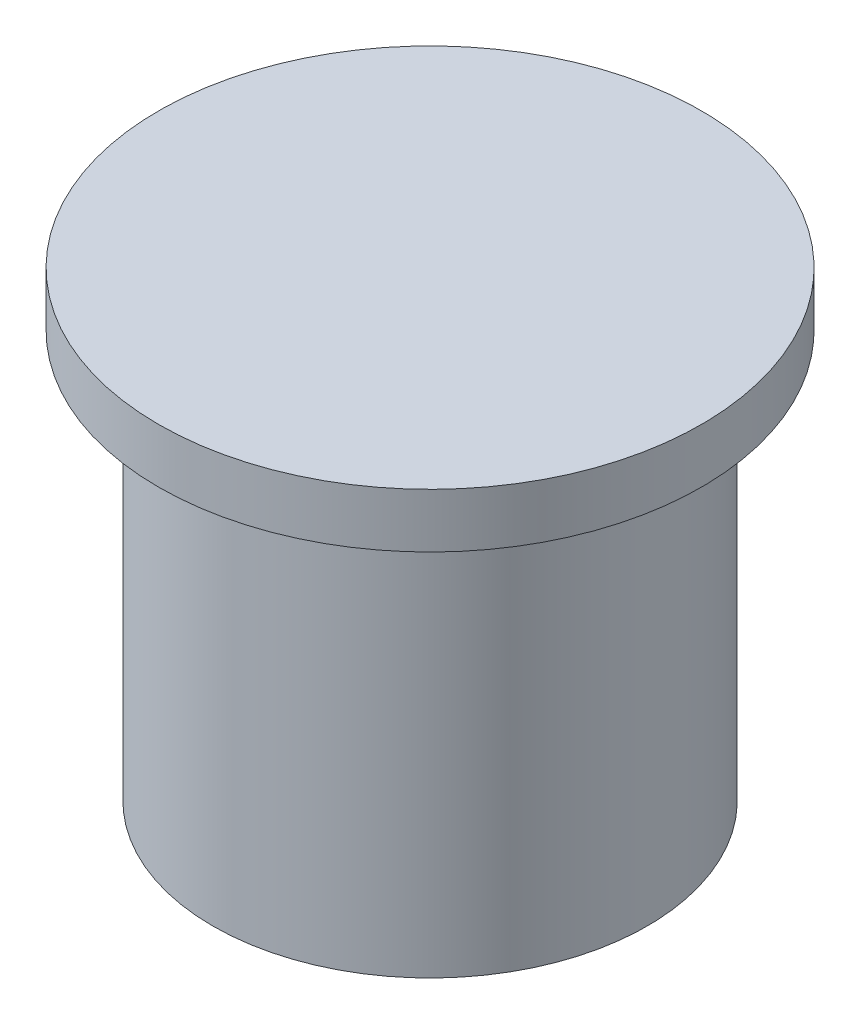
SolidWorks part; units mm, degrees
ref_plane "Спереди" through (0, 0, 0) normal (0, 0, 1) x (1, 0, 0)
ref_plane "Сверху" through (0, 0, 0) normal (0, 1, 0) x (1, 0, 0)
ref_plane "Справа" through (0, 0, 0) normal (1, 0, 0) x (0, 0, -1)
sketch "Эскиз1" plane through (0, 0, 0) normal (0, 1, 0) x (1, 0, 0)
  circle A0 centre (0, 0) radius 80
extrude "Бобышка-Вытянуть1" add sketch "Эскиз1" along normal blind 150
sketch "Эскиз2" plane through (0, 150, 0) normal (0, 1, 0) x (1, 0, 0)
  circle A0 centre (0, 0) radius 100
extrude "Бобышка-Вытянуть2" add sketch "Эскиз2" along normal blind 20
